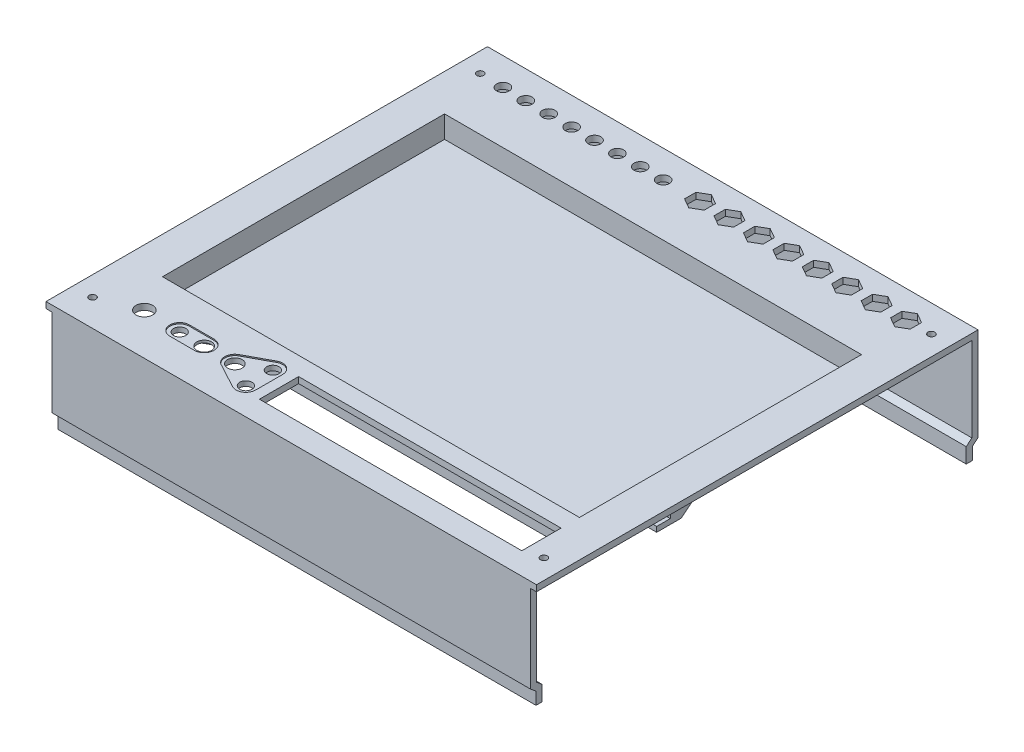
SolidWorks part; units mm, degrees
ref_plane "Alzado" through (0, 0, 0) normal (0, 0, 1) x (1, 0, 0)
ref_plane "Planta" through (0, 0, 0) normal (0, 1, 0) x (1, 0, 0)
ref_plane "Vista lateral" through (0, 0, 0) normal (1, 0, 0) x (0, 0, -1)
sketch "Croquis1" plane through (0, 0, 0) normal (1, 0, 0) x (0, 0, -1)
  line L0 (-90, 6.9261) -> (-90, 45)
  line L1 (-90, 45) -> (90, 45)
  line L2 (90, 45) -> (90, 6.9261)
  line L3 (-90, 6.9261) -> (-87.7, 5)
  line L4 (-87.7, 5) -> (-87.7, 0)
  line L5 (0, 0) -> (0, 88.9733) construction
  line L6 (87.7, 5) -> (87.7, 0)
  line L7 (90, 6.9261) -> (87.7, 5)
  line L8 (-85.2, 6.1672) -> (-85.2, 0)
  line L9 (-87.5, 8.0934) -> (-85.2, 6.1672)
  line L10 (-87.5, 8.0934) -> (-87.5, 42.5)
  line L11 (-87.5, 42.5) -> (87.5, 42.5)
  line L12 (87.5, 42.5) -> (87.5, 8.0934)
  line L13 (87.5, 8.0934) -> (85.2, 6.1672)
  line L14 (85.2, 6.1672) -> (85.2, 0)
  line L15 (85.2, 0) -> (87.7, 0)
  line L16 (-87.7, 0) -> (-85.2, 0)
  point P5 (0, 45)
  dimension "D3" = 5
  dimension "D4" = 45
  dimension "D1" = 180
  dimension "D2" = 3
  dimension "D5" = 2.3
  dimension "D6" = 2.5
extrude "Saliente-Extruir1" add sketch "Croquis1" along normal blind 200 contours L0 L1 L2 L7 L6 L15 L14 L13 L12 L11 L10 L9 L8 L16 L4 L3
sketch "Croquis2" plane through (0, 45, 0) normal (0, 1, 0) x (1, 0, 0)
  line L0 (200, -90) -> (0, -90) construction
  line L1 (189, 60) -> (11, 60)
  line L2 (189, 60) -> (189, -60)
  line L3 (189, -60) -> (11, -60)
  line L4 (11, 60) -> (11, -60)
  line L5 (189, 60) -> (11, -60) construction
  line L6 (189, -60) -> (11, 60) construction
  point P0 (100, 0)
  point P10 (100, -90)
  dimension "D1" = 120
  dimension "D2" = 178
extrude "Saliente-Extruir2" add sketch "Croquis2" against normal blind 11 contours L1 L4 L3 L2
sketch "Croquis3" plane through (0, 45, 0) normal (0, 1, 0) x (1, 0, 0)
  line L0 (200, -90) -> (0, -90) construction
  line L1 (15, 57.5) -> (185, 57.5)
  line L2 (15, 57.5) -> (15, -57.5)
  line L3 (15, -57.5) -> (185, -57.5)
  line L4 (185, 57.5) -> (185, -57.5)
  line L5 (15, 57.5) -> (185, -57.5) construction
  line L6 (15, -57.5) -> (185, 57.5) construction
  line L8 (0, -90) -> (0, 90) construction
  point P0 (100, 0)
  point P8 (100, -90)
  point P13 (0, 0)
  dimension "D1" = 170
  dimension "D2" = 115
extrude "Cortar-Extruir1" cut sketch "Croquis3" against normal blind 9
sketch "Croquis4" plane through (0, 0, 0) normal (0, -1, 0) x (-1, 0, 0)
  line L0 (-200, -90) -> (0, -90) construction
  line L1 (-200, 80) -> (-197.5, 80)
  line L2 (-200, 80) -> (-200, -90)
  line L3 (-200, -90) -> (-197.5, -90)
  line L4 (-197.5, 80) -> (-197.5, -90)
  line L5 (-200, 80) -> (-197.5, -90) construction
  line L6 (-200, -90) -> (-197.5, 80) construction
  line L7 (-200, -87.5) -> (-200, 87.5) construction
  line L8 (-200, 90) -> (0, 90) construction
  line L9 (-2.5, 90) -> (0, 90)
  line L10 (-2.5, 90) -> (-2.5, -90)
  line L11 (-2.5, -90) -> (0, -90)
  line L12 (0, 90) -> (0, -90)
  line L13 (-2.5, 90) -> (0, -90) construction
  line L14 (-2.5, -90) -> (0, 90) construction
  line L15 (0, -87.5) -> (0, 87.5) construction
  point P0 (-198.75, -5)
  point P9 (-1.25, 0)
  dimension "D1" = 2.5
  dimension "D2" = 2.5
extrude "Cortar-Extruir2" cut sketch "Croquis4" against normal up to surface (42.5 mm away) up to face at (100, 42.5, 0)
sketch "Croquis5" plane through (0, 45, 0) normal (0, 1, 0) x (1, 0, 0)
  line L0 (185, 57.5) -> (185, 90) construction
  line L1 (185, -57.5) -> (185, 57.5) construction
  line L2 (185, -57.5) -> (185, 57.5) construction
  line L3 (200, 90) -> (0, 90) construction
  line L4 (188.3221, 78.75) -> (90.1119, 78.75) construction
  line L6 (177.1619, 78.75) -> (179.5434, 74.625) construction
  line L7 (179.5434, 74.625) -> (184.3066, 74.625) construction
  line L8 (184.3066, 74.625) -> (186.6881, 78.75) construction
  line L9 (186.6881, 78.75) -> (184.3066, 82.875) construction
  line L10 (184.3066, 82.875) -> (179.5434, 82.875) construction
  line L11 (179.5434, 82.875) -> (177.1619, 78.75) construction
  circle A0 centre (181.925, 78.75) radius 3.075
  circle A1 centre (169.925, 78.75) radius 3.075
  circle A2 centre (157.925, 78.75) radius 3.075
  circle A3 centre (145.925, 78.75) radius 3.075
  circle A4 centre (133.925, 78.75) radius 3.075
  circle A5 centre (121.925, 78.75) radius 3.075
  circle A6 centre (109.925, 78.75) radius 3.075
  circle A7 centre (97.925, 78.75) radius 3.075
  circle A8 centre (181.925, 78.75) radius 4.125 construction
  dimension "D1" = 6.15
  dimension "D3" = 11.25
  dimension "D4" = 12
  dimension "D5" = 8.25
  dimension "D2" = 8
extrude "Cortar-Extruir3" cut sketch "Croquis5" against normal blind 10
sketch "Croquis6" plane through (0, 34, 0) normal (0, -1, 0) x (1, 0, 0)
  line L0 (185.925, -81.0594) -> (185.925, -76.4406)
  line L1 (177.925, -76.4406) -> (177.925, -81.0594)
  line L2 (177.925, -81.0594) -> (181.925, -83.3688)
  line L3 (181.925, -83.3688) -> (185.925, -81.0594)
  line L4 (185.925, -76.4406) -> (181.925, -74.1312)
  line L5 (181.925, -74.1312) -> (177.925, -76.4406)
  line L6 (169.925, -74.1312) -> (165.925, -76.4406)
  line L7 (165.925, -81.0594) -> (169.925, -83.3688)
  line L8 (169.925, -83.3688) -> (173.925, -81.0594)
  line L9 (173.925, -81.0594) -> (173.925, -76.4406)
  line L10 (165.925, -76.4406) -> (165.925, -81.0594)
  line L11 (173.925, -76.4406) -> (169.925, -74.1312)
  line L12 (157.925, -74.1312) -> (153.925, -76.4406)
  line L13 (153.925, -81.0594) -> (157.925, -83.3688)
  line L14 (157.925, -83.3688) -> (161.925, -81.0594)
  line L15 (161.925, -81.0594) -> (161.925, -76.4406)
  line L16 (153.925, -76.4406) -> (153.925, -81.0594)
  line L17 (161.925, -76.4406) -> (157.925, -74.1312)
  line L18 (145.925, -74.1312) -> (141.925, -76.4406)
  line L19 (141.925, -81.0594) -> (145.925, -83.3688)
  line L20 (145.925, -83.3688) -> (149.925, -81.0594)
  line L21 (149.925, -81.0594) -> (149.925, -76.4406)
  line L22 (141.925, -76.4406) -> (141.925, -81.0594)
  line L23 (149.925, -76.4406) -> (145.925, -74.1312)
  line L24 (133.925, -74.1312) -> (129.925, -76.4406)
  line L25 (129.925, -81.0594) -> (133.925, -83.3688)
  line L26 (133.925, -83.3688) -> (137.925, -81.0594)
  line L27 (137.925, -81.0594) -> (137.925, -76.4406)
  line L28 (129.925, -76.4406) -> (129.925, -81.0594)
  line L29 (137.925, -76.4406) -> (133.925, -74.1312)
  line L30 (121.925, -74.1312) -> (117.925, -76.4406)
  line L31 (117.925, -81.0594) -> (121.925, -83.3688)
  line L32 (121.925, -83.3688) -> (125.925, -81.0594)
  line L33 (125.925, -81.0594) -> (125.925, -76.4406)
  line L34 (117.925, -76.4406) -> (117.925, -81.0594)
  line L35 (125.925, -76.4406) -> (121.925, -74.1312)
  line L36 (109.925, -74.1312) -> (105.925, -76.4406)
  line L37 (105.925, -81.0594) -> (109.925, -83.3688)
  line L38 (109.925, -83.3688) -> (113.925, -81.0594)
  line L39 (113.925, -81.0594) -> (113.925, -76.4406)
  line L40 (105.925, -76.4406) -> (105.925, -81.0594)
  line L41 (113.925, -76.4406) -> (109.925, -74.1312)
  line L42 (97.925, -74.1312) -> (93.925, -76.4406)
  line L43 (93.925, -81.0594) -> (97.925, -83.3688)
  line L44 (97.925, -83.3688) -> (101.925, -81.0594)
  line L45 (101.925, -81.0594) -> (101.925, -76.4406)
  line L46 (93.925, -76.4406) -> (93.925, -81.0594)
  line L47 (101.925, -76.4406) -> (97.925, -74.1312)
  circle A0 centre (181.925, -78.75) radius 4 construction
  circle A1 centre (169.925, -78.75) radius 4 construction
  circle A2 centre (157.925, -78.75) radius 4 construction
  circle A3 centre (145.925, -78.75) radius 4 construction
  circle A4 centre (133.925, -78.75) radius 4 construction
  circle A5 centre (121.925, -78.75) radius 4 construction
  circle A6 centre (109.925, -78.75) radius 4 construction
  circle A7 centre (97.925, -78.75) radius 4 construction
  point P1 (97.925, -78.75)
  point P10 (169.925, -74.1312)
  point P68 (177.9963, -76.3212)
  point P69 (181.925, -74.1312)
  dimension "D1" = 8
  dimension "D2" = 8
extrude "Cortar-Extruir4" cut sketch "Croquis6" against normal blind 11.2
sketch "Croquis7" plane through (0, 45, 0) normal (0, 1, 0) x (1, 0, 0)
  line L0 (0, 78.75) -> (85.4351, 78.75) construction
  line L2 (0, -90) -> (0, 90) construction
  line L3 (200, 90) -> (0, 90) construction
  line L4 (15, 57.5) -> (15, 90) construction
  circle A1 centre (82.8851, 78.75) radius 2.55
  circle A2 centre (73.5515, 78.75) radius 2.55
  circle A3 centre (64.2179, 78.75) radius 2.55
  circle A4 centre (54.8843, 78.75) radius 2.55
  circle A5 centre (45.5507, 78.75) radius 2.55
  circle A6 centre (36.2172, 78.75) radius 2.55
  circle A7 centre (26.8836, 78.75) radius 2.55
  circle A8 centre (17.55, 78.75) radius 2.55
  point P2 (18.6888, 78.75)
  dimension "D1" = 5.1
  dimension "D4" = 65.3351
  dimension "D3" = 11.25
  dimension "D2" = 8
extrude "Cortar-Extruir5" cut sketch "Croquis7" against normal blind 10
sketch "Croquis9" plane through (0, 45, 0) normal (0, 1, 0) x (1, 0, 0)
  line L1 (185, -81) -> (78, -81)
  line L2 (185, -81) -> (185, -65)
  line L3 (185, -65) -> (78, -65)
  line L4 (78, -81) -> (78, -65)
  line L5 (185, -81) -> (78, -65) construction
  line L6 (185, -65) -> (78, -81) construction
  line L7 (185, -57.5) -> (185, 57.5) construction
  line L8 (200, -90) -> (0, -90) construction
  point P0 (131.5, -73)
  point P5 (131.5, -78.75)
  point P10 (0, 0)
  dimension "D1" = 107
  dimension "D2" = 16
  dimension "D3" = 17
extrude "Cortar-Extruir7" cut sketch "Croquis9" against normal blind 4
sketch "Croquis8" plane through (0, 45, 0) normal (0, 1, 0) x (1, 0, 0)
  line L0 (47.5, -73) -> (47.5, -77.6188) construction
  line L1 (63, -73) -> (15, -73) construction
  line L2 (47.5, -77.6188) -> (51.5, -75.3094) construction
  line L3 (15, 57.5) -> (15, -57.5) construction
  line L4 (200, -90) -> (0, -90) construction
  line L5 (0, -90) -> (0, 90) construction
  line L6 (51.5, -75.3094) -> (51.5, -70.6906) construction
  line L7 (51.5, -70.6906) -> (47.5, -68.3812) construction
  line L8 (47.5, -68.3812) -> (43.5, -70.6906) construction
  line L9 (43.5, -70.6906) -> (43.5, -75.3094) construction
  line L10 (43.5, -75.3094) -> (47.5, -77.6188) construction
  line L11 (63, -73) -> (70, -73) construction
  line L12 (70, -73) -> (70, -78.5) construction
  line L13 (70, -78.5) -> (60, -73) construction
  line L14 (60, -73) -> (70, -67.5) construction
  line L15 (70, -67.5) -> (70, -73) construction
  line L18 (78, -81) -> (63, -81) construction
  line L19 (78, -65) -> (62.9966, -65) construction
  circle A0 centre (60, -73) radius 3
  circle A1 centre (37.5, -73) radius 2.5
  circle A2 centre (23.1, -73) radius 3.4
  circle A3 centre (23.1, -73) radius 8.1 construction
  circle A4 centre (70, -73) radius 2.5 construction
  circle A5 centre (47.5, -73) radius 3
  circle A6 centre (47.5, -73) radius 4 construction
  circle A7 centre (70, -78.5) radius 2.5
  circle A8 centre (70, -67.5) radius 2.5
  point P32 (70, -69.3812)
  point P33 (70, -78.4213)
  dimension "D1" = 6
  dimension "D2" = 17
  dimension "D3" = 5
  dimension "D5" = 6.8
  dimension "D7" = 16.2
  dimension "D4" = 5
  dimension "D6" = 6
  dimension "D10" = 70
  dimension "D11" = 60
  dimension "D14" = 5
  dimension "D15" = 5
  dimension "D8" = 37.5
  dimension "D9" = 47.5
  dimension "D12" = 23.1
  dimension "D13" = 8
extrude "Cortar-Extruir6" cut sketch "Croquis8" against normal blind 4
sketch "Croquis10" plane through (189, 0, 0) normal (1, 0, 0) x (0, 0, -1)
  line L0 (-87.5, 28.6897) -> (-84.9, 28.6897)
  line L1 (-84.9, 28.6897) -> (-84.9, 30.0897)
  line L2 (-84.9, 30.0897) -> (-87.5, 30.0897)
  line L3 (-87.5, 30.0897) -> (-87.5, 32.2897)
  line L4 (-87.5, 32.2897) -> (-84.9, 32.2897)
  line L5 (-84.9, 32.2897) -> (-84.9, 33.6916)
  line L6 (-84.9, 33.6916) -> (-87.5, 33.6916)
  line L7 (-90, 42.5) -> (87.5, 42.5) construction
  line L8 (60, 34) -> (-60, 34) construction
  line L9 (-15, 34) -> (-15, 32.0127)
  line L10 (-15, 32.0127) -> (-20, 28)
  line L11 (-20, 28) -> (-30, 28)
  line L12 (-30, 28) -> (-30, 30.0897)
  line L13 (-30, 30.0897) -> (-24.4616, 30.0897)
  line L14 (-24.4616, 30.0897) -> (-24.4616, 34)
  line L15 (-24.4616, 34) -> (-15, 34)
  line L16 (-87.5, 42.5) -> (-87.5, 8.0934) construction
  line L17 (-87.5, 28.6897) -> (-87.5, 30.0897)
  line L18 (-87.5, 33.6916) -> (-87.5, 32.2897)
  point P24 (-30, 29.0449)
  line M16 (-60, 34) -> (60, 34)
  dimension "D1" = 1.4
  dimension "D2" = 1.4019
  dimension "D3" = 2.6
  dimension "D4" = 2.2
  dimension "D5" = 8.8084
  dimension "D6" = 10
  dimension "D7" = 15
  dimension "D8" = 30
  dimension "D9" = 6
extrude "Saliente-Extruir3" add sketch "Croquis10" against normal blind 123 contours L17 L0 L1 L2 | L6 L18 L4 L5 | L14 L13 L12 L11 L10 L9 M16 region at (189, 29.3897, 86.2) region at (189, 32.9907, 86.2) region at (189, 30.8979, 21.7465)
sketch "Croquis11" plane through (0, 42.5, 0) normal (0, -1, 0) x (1, 0, 0)
  line L0 (47.5, 73) -> (47.5, 77.6188) construction
  line L1 (47.5, 4691.3588) -> (-3952.116, 2382.1794)
  line L2 (-3952.116, 2382.1794) -> (-3952.116, -2236.1794)
  line L3 (-3952.116, -2236.1794) -> (47.5, -4545.3588)
  line L4 (47.5, -4545.3588) -> (4047.116, -2236.1794)
  line L5 (4047.116, -2236.1794) -> (4047.116, 2382.1794)
  line L6 (4047.116, 2382.1794) -> (47.5, 4691.3588)
  line L7 (47.5, 68.3812) -> (51.5, 70.6906)
  line L8 (51.5, 70.6906) -> (51.5, 75.3094)
  line L9 (51.5, 75.3094) -> (47.5, 77.6188)
  line L10 (47.5, 77.6188) -> (43.5, 75.3094)
  line L11 (43.5, 75.3094) -> (43.5, 70.6906)
  line L12 (43.5, 70.6906) -> (47.5, 68.3812)
  circle A0 centre (47.5, 73) radius 3999.616 construction
  circle A1 centre (47.5, 73) radius 4 construction
  dimension "D1" = 8
extrude "Cortar-Extruir10" cut sketch "Croquis11" against normal blind 1 flip side to cut
sketch "Croquis12" plane through (0, 45, 0) normal (0, 1, 0) x (1, 0, 0)
  line L0 (68.1021, -82.0211) -> (58.0562, -76.6061)
  line L1 (68.1021, -63.9789) -> (58.0562, -69.3939)
  line L2 (74, -78.5) -> (74, -67.5)
  line L3 (47.5, -73) -> (37.5, -73) construction
  line L4 (47.5, -77) -> (37.5, -77)
  line L5 (47.5, -69) -> (37.5, -69)
  circle A0 centre (70, -67.5) radius 3 construction
  arc A2 (74, -67.5) -> (68.1021, -63.9789) centre (70, -67.5) ccw
  arc A3 (68.1021, -82.0211) -> (74, -78.5) centre (70, -78.5) ccw
  arc A10 (47.5, -77) -> (47.5, -69) centre (47.5, -73) ccw
  arc A11 (37.5, -69) -> (37.5, -77) centre (37.5, -73) ccw
  circle A12 centre (47.5, -73) radius 3 construction
  circle A13 centre (37.5, -73) radius 3 construction
  arc A14 (58.0562, -69.3939) -> (58.0562, -76.6061) centre (60, -73) ccw
  circle A15 centre (60, -73) radius 3 construction
  circle A16 centre (70, -78.5) radius 3 construction
  point P13 (74, -78.5)
  point P16 (42.5, -73)
  point P21 (33.5, -73)
  point P24 (51.5, -73)
  point P35 (74, -67.5)
  point P36 (0, 0)
  point P37 (68.2166, -63.9196)
  point P38 (68.1021, -63.9789)
  point P39 (71.835, -61.9668)
  point P40 (74, -81.5263)
  point P41 (0, 0)
  point P42 (74, -67.5)
  point P43 (0, 0)
  point P44 (74, -67.5)
  point P45 (0, 0)
  point P46 (74, -61.9668)
  dimension "D3" = 6
  dimension "D1" = 1.0966
  dimension "D2" = 6
  dimension "D5" = 6
  dimension "D7" = 1
  dimension "D8" = 1
  dimension "D4" = 1
  dimension "D6" = 1
extrude "Cortar-Extruir11" cut sketch "Croquis12" against normal blind 0.5
sketch "Croquis13" plane through (66, 0, 0) normal (-1, 0, 0) x (0, 0, 1)
  line L0 (24.4616, 34) -> (15, 34) construction
  line L1 (87.5, 33.6916) -> (84.9, 33.6916)
  line L2 (87.5, 33.6916) -> (87.5, 28.6897)
  line L3 (87.5, 28.6897) -> (84.9, 28.6897)
  line L4 (84.9, 33.6916) -> (84.9, 28.6897)
  line L5 (87.5, 33.6916) -> (84.9, 28.6897) construction
  line L6 (87.5, 28.6897) -> (84.9, 33.6916) construction
  line L7 (15, 34) -> (30, 34)
  line L8 (15, 34) -> (15, 32.0127)
  line L9 (20, 28) -> (30, 28)
  line L10 (30, 34) -> (30, 28)
  line L11 (15, 34) -> (30, 28) construction
  line L12 (18.3368, 29.3347) -> (30, 34) construction
  line L13 (15, 34) -> (15, 32.0127) construction
  line L14 (20, 28) -> (15, 32.0127)
  line L15 (84.9, 33.6916) -> (87.5, 33.6916) construction
  point P0 (86.2, 31.1907)
  point P6 (22.5, 31)
extrude "Saliente-Extruir4" add sketch "Croquis13" along normal blind 0.5
fillet "Redondeo7" radius 0.5 2 edges at (127.25, 33.6916, 87.5) (127.25, 28.6897, 87.5)
fillet "Redondeo8" radius 3 2 edges at (189, 33.2407, 87.5) (189, 29.1397, 87.5)
fillet "Redondeo9" radius 1 2 edges at (189, 32.9907, 84.9) (189, 29.3897, 84.9)
sketch "Croquis14" plane through (0, 45, 0) normal (0, 1, 0) x (1, 0, 0)
  line L0 (200, -90) -> (0, -90) construction
  line L1 (200, -90) -> (200, 90) construction
  line L2 (0, 0) -> (200, 0) construction
  line L3 (100, -90) -> (100, 90) construction
  line L4 (200, 90) -> (0, 90) construction
  circle A0 centre (192, -79.01) radius 1.4
  circle A1 centre (192, 79.01) radius 1.4
  circle A2 centre (8, 79.01) radius 1.4
  circle A3 centre (8, -79.01) radius 1.4
  dimension "D1" = 10.99
  dimension "D3" = 2.8
  dimension "D2" = 8
extrude "Cortar-Extruir12" cut sketch "Croquis14" against normal blind 5
